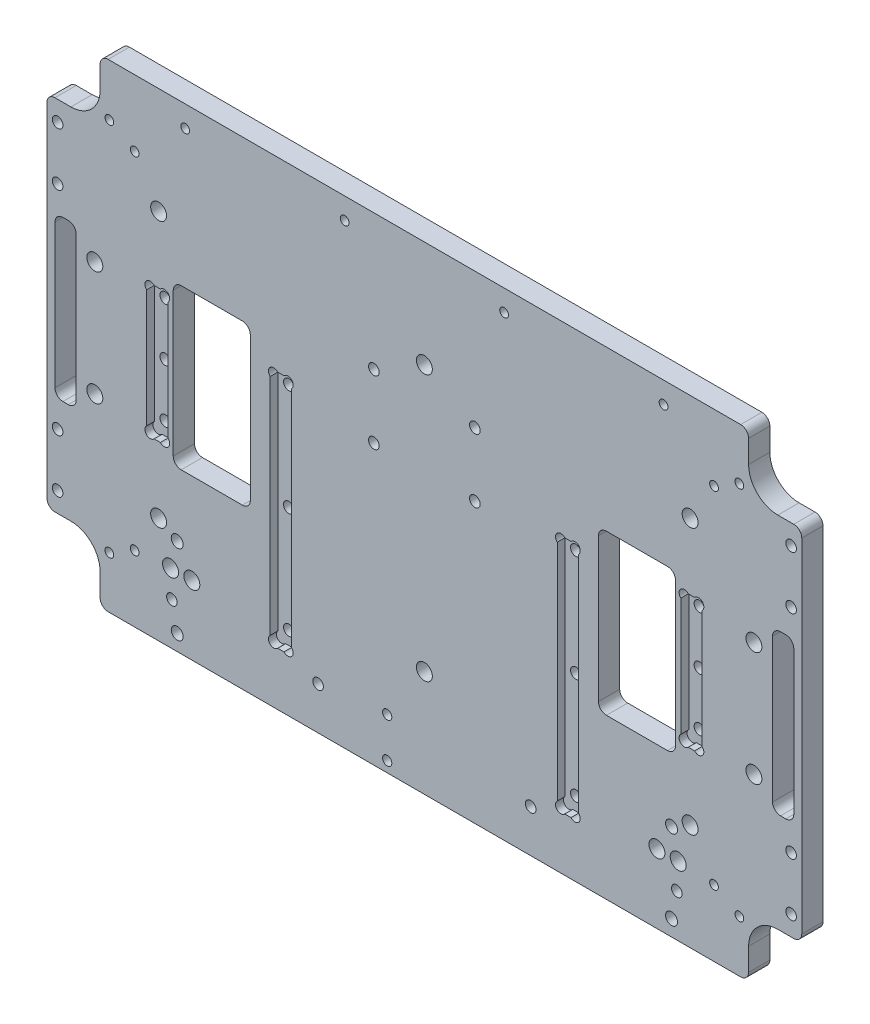
SolidWorks part; units mm, degrees
ref_plane "Front" through (0, 0, 0) normal (0, 0, 1) x (1, 0, 0)
ref_plane "Top" through (0, 0, 0) normal (0, 1, 0) x (1, 0, 0)
ref_plane "Right" through (0, 0, 0) normal (1, 0, 0) x (0, 0, -1)
sketch "Esquisse1" plane through (0, 0, 0) normal (0, 0, 1) x (1, 0, 0)
  line L1 (0, 0) -> (284, 0)
  line L2 (0, 0) -> (0, 180)
  line L3 (0, 180) -> (284, 180)
  line L4 (284, 0) -> (284, 180)
  dimension "D1" = 284
  dimension "D2" = 180
extrude "Boss.-Extru.1" add sketch "Esquisse1" along normal blind 8
sketch "Esquisse2" plane through (0, 0, 8) normal (0, 0, 1) x (1, 0, 0)
  line L0 (142, 180) -> (142, 0) construction
  line L1 (47.5, 60) -> (76.5, 60)
  line L2 (47.5, 60) -> (47.5, 120)
  line L3 (47.5, 120) -> (76.5, 120)
  line L4 (76.5, 60) -> (76.5, 120)
  line L5 (284, 180) -> (0, 180) construction
  line L6 (0, 0) -> (284, 0) construction
  line L7 (76.5, 90) -> (142, 90) construction
  line L8 (62, 60) -> (62, 120) construction
  line L9 (47.5, 90) -> (11, 90) construction
  line L10 (7, 60) -> (7, 120) construction
  line L11 (3, 60) -> (11, 60)
  line L12 (3, 60) -> (3, 120)
  line L13 (3, 120) -> (11, 120)
  line L14 (11, 60) -> (11, 120)
  line L15 (277, 60) -> (277, 120) construction
  line L16 (236.5, 90) -> (273, 90) construction
  line L17 (222, 60) -> (222, 120) construction
  line L18 (273, 60) -> (273, 120)
  line L19 (281, 120) -> (273, 120)
  line L20 (281, 60) -> (281, 120)
  line L21 (281, 60) -> (273, 60)
  line L22 (207.5, 60) -> (207.5, 120)
  line L23 (236.5, 120) -> (207.5, 120)
  line L24 (236.5, 60) -> (236.5, 120)
  line L25 (236.5, 60) -> (207.5, 60)
  dimension "D1" = 90
  dimension "D2" = 60
  dimension "D3" = 29
  dimension "D4" = 160
  dimension "D5" = 8
  dimension "D6" = 60
  dimension "D7" = 270
extrude "Enlèv. mat.-Extru.1" cut sketch "Esquisse2" against normal through all
sketch "Esquisse3" plane through (0, 0, 8) normal (0, 0, 1) x (1, 0, 0)
  line L0 (0, 172) -> (284, 172) construction
  line L1 (0, 180) -> (0, 0) construction
  line L2 (284, 0) -> (284, 180) construction
  line L3 (112, 172) -> (112, 180.3897) construction
  line L5 (172, 172) -> (172, 180.3897) construction
  line L6 (172, 180.3897) -> (112, 180.3897) construction
  line L7 (142, 180.3897) -> (142, 180) construction
  line L8 (284, 180) -> (0, 180) construction
  circle A0 centre (112, 172) radius 1.65
  circle A1 centre (172, 172) radius 1.65
  circle A2 centre (232, 172) radius 1.65
  circle A4 centre (52, 172) radius 1.65
  dimension "D1" = 3.3
  dimension "D2" = 4
  dimension "D3" = 8
  dimension "D4" = 60
extrude "Enlèv. mat.-Extru.2" cut sketch "Esquisse3" against normal up to vertex (8 mm away) up to point (284, 180, 0)
sketch "Esquisse4" plane through (0, 0, 8) normal (0, 0, 1) x (1, 0, 0)
  line L0 (142, 0) -> (142, 180) construction
  line L1 (84, 110) -> (92, 110)
  line L2 (84, 110) -> (84, 20)
  line L3 (84, 20) -> (92, 20)
  line L4 (92, 110) -> (92, 20)
  line L5 (0, 0) -> (284, 0) construction
  line L6 (284, 180) -> (0, 180) construction
  line L8 (76.5, 60) -> (76.5, 120) construction
  line L9 (192, 110) -> (192, 20)
  line L10 (200, 20) -> (192, 20)
  line L11 (200, 110) -> (200, 20)
  line L12 (200, 110) -> (192, 110)
  line L13 (47.5, 120) -> (47.5, 60) construction
  line L14 (37.5, 115) -> (45.5, 115)
  line L15 (37.5, 115) -> (37.5, 65)
  line L16 (37.5, 65) -> (45.5, 65)
  line L17 (45.5, 115) -> (45.5, 65)
  line L18 (45.5, 90) -> (47.5, 90) construction
  line L19 (238.5, 90) -> (236.5, 90) construction
  line L20 (238.5, 115) -> (238.5, 65)
  line L21 (246.5, 65) -> (238.5, 65)
  line L22 (246.5, 115) -> (246.5, 65)
  line L23 (246.5, 115) -> (238.5, 115)
  line L24 (47.5, 60) -> (76.5, 60) construction
  dimension "D1" = 40
  dimension "D2" = 90
  dimension "D3" = 8
  dimension "D4" = 7.5
  dimension "D5" = 8
  dimension "D6" = 2
  dimension "D7" = 50
extrude "Enlèv. mat.-Extru.3" cut sketch "Esquisse4" against normal blind 3
sketch "Esquisse5" plane through (0, 0, 8) normal (0, 0, 1) x (1, 0, 0)
  line L0 (142, 0) -> (142, 124.0722) construction
  line L2 (142, 117) -> (121.1311, 117) construction
  line L3 (0, 180) -> (0, 0) construction
  circle A0 centre (123, 129) radius 2
  circle A1 centre (123, 105) radius 2
  circle A2 centre (161, 105) radius 2
  circle A3 centre (161, 129) radius 2
  circle A5 centre (112, 172) radius 1.65 construction
  dimension "D1" = 38
  dimension "D2" = 4
  dimension "D3" = 24
  dimension "D4" = 55
  dimension "D5" = 142
extrude "Enlèv. mat.-Extru.4" cut sketch "Esquisse5" against normal through all
sketch "Esquisse6" plane through (0, 0, 8) normal (0, 0, 1) x (1, 0, 0)
  line L0 (142, 0) -> (142, 119.0936) construction
  line L1 (0, 0) -> (284, 0) construction
  line L2 (11, 90) -> (29.8915, 90) construction
  line L4 (11, 60) -> (11, 120) construction
  line L5 (273, 90) -> (254.1085, 90) construction
  circle A0 centre (18, 111.5) radius 3
  circle A1 centre (18, 68.5) radius 3
  circle A2 centre (266, 68.5) radius 3
  circle A3 centre (266, 111.5) radius 3
  dimension "D3" = 6
  dimension "D1" = 21.5
  dimension "D2" = 7
extrude "Enlèv. mat.-Extru.5" cut sketch "Esquisse6" against normal through all
sketch "Esquisse8" plane through (0, 0, 8) normal (0, 0, 1) x (1, 0, 0)
  line L0 (142, 180) -> (142, 109.7669) construction
  line L1 (0, 180) -> (20, 180)
  line L2 (0, 180) -> (0, 157.5)
  line L3 (0, 157.5) -> (20, 157.5)
  line L4 (20, 180) -> (20, 157.5)
  line L5 (284, 180) -> (0, 180) construction
  line L6 (264, 180) -> (264, 157.5)
  line L7 (284, 157.5) -> (264, 157.5)
  line L8 (284, 180) -> (284, 157.5)
  line L9 (284, 180) -> (264, 180)
  line L10 (264, 0) -> (264, 22.5)
  line L11 (0, 0) -> (20, 0)
  line L12 (0, 0) -> (0, 22.5)
  line L13 (0, 22.5) -> (20, 22.5)
  line L14 (20, 0) -> (20, 22.5)
  line L15 (284, 22.5) -> (264, 22.5)
  line L16 (284, 0) -> (284, 22.5)
  line L17 (284, 0) -> (264, 0)
  dimension "D1" = 22.5
  dimension "D2" = 20
  dimension "D3" = 22.5
extrude "Enlèv. mat.-Extru.7" cut sketch "Esquisse8" against normal through all
fillet "Congé1" radius 11 4 edges at (20, 157.5, 4) (264, 157.5, 4) (264, 22.5, 4) (20, 22.5, 4)
sketch "Esquisse7" plane through (0, 0, 8) normal (0, 0, 1) x (1, 0, 0)
  line L0 (142, 180) -> (142, 7.3256) construction
  line L1 (264, 180) -> (20, 180) construction
  line L2 (23.4737, 160.5) -> (33, 155) construction
  line L3 (264, 180) -> (20, 180) construction
  line L4 (260.5263, 160.5) -> (251, 155) construction
  line L5 (33, 155) -> (33, 25) construction
  line L6 (33, 90) -> (100.6533, 90) construction
  line L7 (23.4737, 19.5) -> (33, 25) construction
  line L8 (20, 0) -> (264, 0) construction
  line L9 (260.5263, 19.5) -> (251, 25) construction
  circle A0 centre (33, 155) radius 1.65
  circle A1 centre (23.4737, 160.5) radius 1.65
  circle A2 centre (260.5263, 160.5) radius 1.65
  circle A3 centre (251, 155) radius 1.65
  circle A5 centre (23.4737, 19.5) radius 1.65
  circle A6 centre (33, 25) radius 1.65
  circle A7 centre (251, 25) radius 1.65
  circle A8 centre (260.5263, 19.5) radius 1.65
  dimension "D1" = 3.3
  dimension "D5" = 25
  dimension "D2" = 11
  dimension "D3" = 109
  dimension "D4" = 30
  dimension "D6" = 25
extrude "Enlèv. mat.-Extru.6" cut sketch "Esquisse7" against normal through all
fillet "Congé2" radius 3 16 edges at (281, 60, 4) (273, 60, 4) (281, 120, 4) (273, 120, 4) (236.5, 120, 4) (207.5, 120, 4) (236.5, 60, 4) (207.5, 60, 4) (76.5, 60, 4) (47.5, 60, 4) (76.5, 120, 4) (47.5, 120, 4) (11, 120, 4) (3, 120, 4) (3, 60, 4) (11, 60, 4)
sketch "Esquisse9" plane through (0, 0, 8) normal (0, 0, 1) x (1, 0, 0)
  line L0 (37.5, 115) -> (38.8435, 113.6565) construction
  line L1 (45.5, 115) -> (37.5, 115) construction
  line L2 (41.5, 115) -> (41.5, 118.2808) construction
  line L3 (45.5, 115) -> (37.5, 115) construction
  line L4 (45.5, 115) -> (44.1565, 113.6565) construction
  line L5 (45.5, 90) -> (42.8729, 90) construction
  line L6 (45.5, 65) -> (45.5, 115) construction
  line L7 (45.5, 65) -> (44.1565, 66.3435) construction
  line L8 (37.5, 65) -> (38.8435, 66.3435) construction
  line L9 (45.5, 90) -> (238.5, 90) construction
  line L10 (238.5, 115) -> (238.5, 65) construction
  line L11 (142, 90) -> (142, 121.5895) construction
  line L12 (246.5, 65) -> (245.1565, 66.3435) construction
  line L13 (238.5, 65) -> (239.8435, 66.3435) construction
  line L14 (238.5, 90) -> (241.1271, 90) construction
  line L15 (238.5, 115) -> (239.8435, 113.6565) construction
  line L16 (242.5, 115) -> (242.5, 118.2808) construction
  line L17 (246.5, 115) -> (245.1565, 113.6565) construction
  line L18 (84, 110) -> (85.3435, 108.6565) construction
  line L19 (92, 110) -> (84, 110) construction
  line L20 (88, 110) -> (88, 112.2434) construction
  line L21 (92, 110) -> (84, 110) construction
  line L22 (92, 110) -> (90.6565, 108.6565) construction
  line L23 (84, 65) -> (89.3356, 65) construction
  line L24 (84, 110) -> (84, 20) construction
  line L25 (92, 20) -> (90.6565, 21.3435) construction
  line L26 (88, 20) -> (88, 17.7566) construction
  line L27 (84, 20) -> (85.3435, 21.3435) construction
  line L28 (200, 20) -> (198.6565, 21.3435) construction
  line L29 (196, 20) -> (196, 17.7566) construction
  line L30 (192, 20) -> (193.3435, 21.3435) construction
  line L31 (200, 65) -> (194.6644, 65) construction
  line L32 (192, 110) -> (193.3435, 108.6565) construction
  line L33 (196, 110) -> (196, 112.2434) construction
  line L34 (200, 110) -> (198.6565, 108.6565) construction
  circle A0 centre (38.8435, 113.6565) radius 2
  circle A1 centre (44.1565, 113.6565) radius 2
  circle A2 centre (44.1565, 66.3435) radius 2
  circle A3 centre (38.8435, 66.3435) radius 2
  circle A4 centre (245.1565, 66.3435) radius 2
  circle A5 centre (239.8435, 66.3435) radius 2
  circle A6 centre (239.8435, 113.6565) radius 2
  circle A7 centre (245.1565, 113.6565) radius 2
  circle A8 centre (85.3435, 108.6565) radius 2
  circle A9 centre (90.6565, 108.6565) radius 2
  circle A10 centre (90.6565, 21.3435) radius 2
  circle A11 centre (85.3435, 21.3435) radius 2
  circle A12 centre (198.6565, 21.3435) radius 2
  circle A13 centre (193.3435, 21.3435) radius 2
  circle A14 centre (193.3435, 108.6565) radius 2
  circle A15 centre (198.6565, 108.6565) radius 2
  dimension "D1" = 4
  dimension "D6" = 4
  dimension "D2" = 45
  dimension "D3" = 1.9
  dimension "D4" = 45
  dimension "D5" = 1.9
extrude "Enlèv. mat.-Extru.8" cut sketch "Esquisse9" against normal up to vertex (3 mm away) up to point (37.5, 65, 5)
fillet "Congé3" radius 3 8 edges at (264, 180, 4) (284, 157.5, 4) (284, 22.5, 4) (264, 0, 4) (20, 0, 4) (0, 22.5, 4) (0, 157.5, 4) (20, 180, 4)
sketch "Esquisse10" plane through (0, 0, 5) normal (0, 0, 1) x (1, 0, 0)
  line L0 (41.5, 115) -> (41.5, 65) construction
  line L1 (42.6749, 115) -> (40.3251, 115) construction
  line L2 (40.3251, 65) -> (42.6749, 65) construction
  line L3 (41.5, 90) -> (37.5, 90) construction
  line L4 (37.5, 112.1749) -> (37.5, 67.8251) construction
  line L5 (88, 110) -> (88, 20) construction
  line L6 (89.1749, 110) -> (86.8251, 110) construction
  line L7 (86.8251, 20) -> (89.1749, 20) construction
  line L8 (88, 65) -> (84, 65) construction
  line L9 (84, 107.1749) -> (84, 22.8251) construction
  line L10 (142, 0) -> (142, 180) construction
  line L11 (23, 0) -> (261, 0) construction
  line L12 (261, 180) -> (23, 180) construction
  line L13 (196, 65) -> (200, 65) construction
  line L14 (196, 110) -> (196, 20) construction
  line L15 (242.5, 90) -> (246.5, 90) construction
  line L16 (242.5, 115) -> (242.5, 65) construction
  circle A0 centre (41.5, 90) radius 2
  circle A1 centre (41.5, 70) radius 2
  circle A2 centre (41.5, 110) radius 2
  circle A3 centre (88, 65) radius 2
  circle A4 centre (88, 25) radius 2
  circle A5 centre (88, 105) radius 2
  circle A6 centre (196, 105) radius 2
  circle A7 centre (196, 25) radius 2
  circle A8 centre (196, 65) radius 2
  circle A9 centre (242.5, 110) radius 2
  circle A10 centre (242.5, 70) radius 2
  circle A11 centre (242.5, 90) radius 2
  dimension "D1" = 4
  dimension "D2" = 20
  dimension "D3" = 40
extrude "Enlèv. mat.-Extru.9" cut sketch "Esquisse10" against normal through all
sketch "Esquisse11" plane through (0, 0, 8) normal (0, 0, 1) x (1, 0, 0)
  line L0 (142, 0) -> (142, 52.4414) construction
  line L1 (23, 0) -> (261, 0) construction
  line L2 (142, 16) -> (47, 16) construction
  line L3 (86.8251, 20) -> (89.1749, 20) construction
  line L4 (46.5, 26) -> (54.5, 26) construction
  line L5 (237.5, 26) -> (229.5, 26) construction
  circle A0 centre (47, 16) radius 2
  circle A1 centre (237, 16) radius 2
  circle A2 centre (102, 16) radius 2
  circle A3 centre (46.5, 26) radius 3
  circle A4 centre (54.5, 26) radius 3
  circle A5 centre (229.5, 26) radius 3
  circle A6 centre (237.5, 26) radius 3
  circle A7 centre (182, 16) radius 2
  point P10 (94.5, 16)
  point P13 (88, 20)
  dimension "D1" = 4
  dimension "D2" = 190
  dimension "D4" = 8
  dimension "D5" = 10
  dimension "D7" = 6
  dimension "D8" = 80
  dimension "D3" = 4
  dimension "D6" = 87.5
extrude "Enlèv. mat.-Extru.10" cut sketch "Esquisse11" against normal through all
sketch "Esquisse12" plane through (0, 0, 8) normal (0, 0, 1) x (1, 0, 0)
  line L0 (128, 0) -> (128, 19) construction
  line L1 (23, 0) -> (261, 0) construction
  circle A0 centre (128, 4) radius 1.75
  circle A1 centre (128, 19) radius 1.75
  dimension "D1" = 15
  dimension "D2" = 3.5
  dimension "D3" = 4
  dimension "D4" = 128
extrude "Enlèv. mat.-Extru.11" cut sketch "Esquisse12" against normal through all
sketch "Esquisse13" plane through (0, 0, 8) normal (0, 0, 1) x (1, 0, 0)
  line L0 (4, 157.5) -> (4, 22.5) construction
  line L1 (3, 157.5) -> (9, 157.5) construction
  line L2 (9, 22.5) -> (3, 22.5) construction
  line L3 (0, 154.5) -> (0, 25.5) construction
  line L4 (11, 90) -> (4, 90) construction
  line L5 (11, 63) -> (11, 117) construction
  line L6 (142, 0) -> (142, 180) construction
  line L7 (23, 0) -> (261, 0) construction
  line L8 (261, 180) -> (23, 180) construction
  line L9 (273, 90) -> (280, 90) construction
  line L10 (280, 157.5) -> (280, 22.5) construction
  circle A0 centre (4, 30) radius 2
  circle A1 centre (4, 50) radius 2
  circle A2 centre (4, 130) radius 2
  circle A3 centre (4, 150) radius 2
  circle A4 centre (280, 150) radius 2
  circle A5 centre (280, 130) radius 2
  circle A6 centre (280, 50) radius 2
  circle A7 centre (280, 30) radius 2
  dimension "D2" = 20
  dimension "D3" = 4
  dimension "D4" = 80
  dimension "D1" = 4
extrude "Enlèv. mat.-Extru.12" cut sketch "Esquisse13" against normal through all
sketch "Esquisse14" plane through (0, 0, 8) normal (0, 0, 1) x (1, 0, 0)
  line L0 (142, 0) -> (142, 180) construction
  line L1 (23, 0) -> (261, 0) construction
  line L2 (261, 180) -> (23, 180) construction
  line L3 (142, 90) -> (0, 90) construction
  line L4 (0, 154.5) -> (0, 25.5) construction
  line L5 (142, 40) -> (42, 40) construction
  circle A0 centre (42, 140) radius 3
  circle A1 centre (42, 40) radius 3
  circle A2 centre (242, 40) radius 3
  circle A3 centre (242, 140) radius 3
  circle A4 centre (142, 40) radius 3
  circle A5 centre (142, 140) radius 3
  dimension "D3" = 6
  dimension "D1" = 200
  dimension "D2" = 50
extrude "fixations_usinage" cut sketch "Esquisse14" against normal through all both and the other way through all
sketch "Esquisse15" plane through (0, 0, 8) normal (0, 0, 1) x (1, 0, 0)
  line L0 (142, 0) -> (142, 73.8911) construction
  line L1 (23, 0) -> (261, 0) construction
  line L2 (142, 21) -> (212.0027, 21) construction
  circle A0 centre (235, 6) radius 2.25
  circle A1 centre (235, 36) radius 2.25
  circle A2 centre (49, 36) radius 2.25
  circle A3 centre (49, 6) radius 2.25
  dimension "D1" = 4.5
  dimension "D2" = 30
  dimension "D3" = 186
  dimension "D4" = 6
extrude "Enlèv. mat.-Extru.13" cut sketch "Esquisse15" against normal through all both and the other way through all
